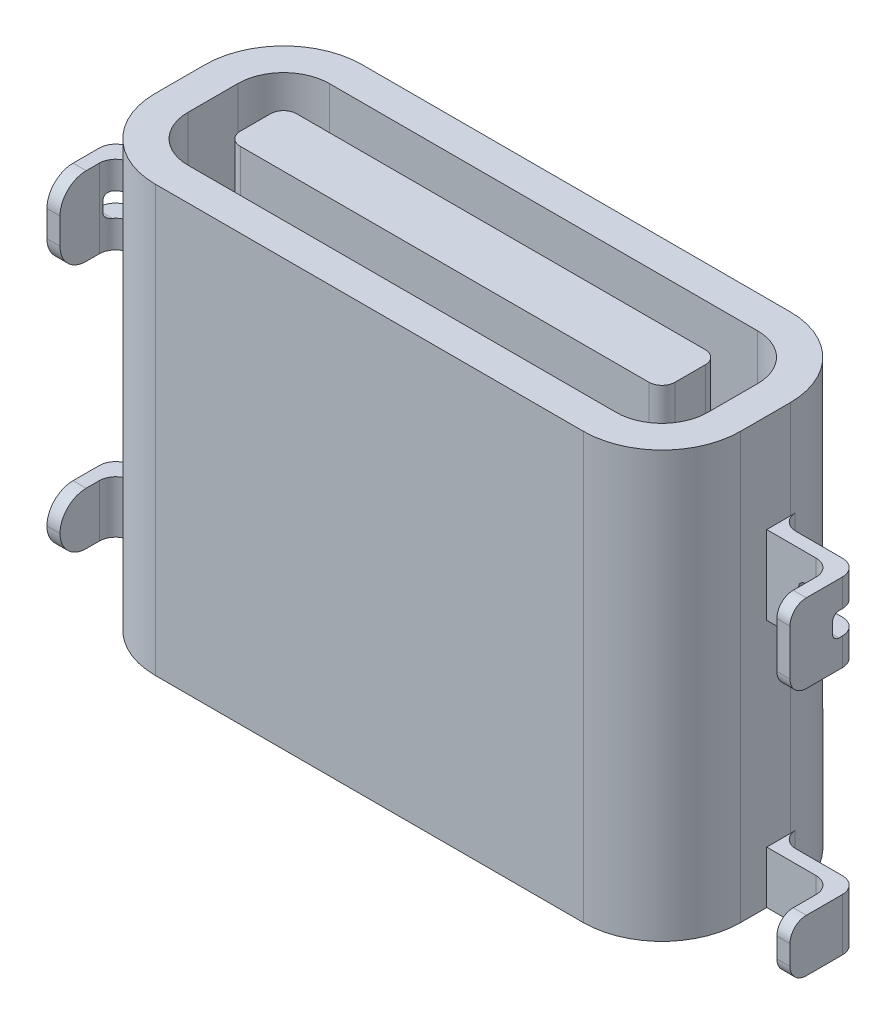
SolidWorks part; units mm, degrees
ref_plane "Front" through (0, 0, 0) normal (0, 0, 1) x (1, 0, 0)
ref_plane "Top" through (0, 0, 0) normal (0, 1, 0) x (1, 0, 0)
ref_plane "Right" through (0, 0, 0) normal (1, 0, 0) x (0, 0, -1)
sketch "Sketch1" plane through (0, 0, 0) normal (0, 1, 0) x (1, 0, 0)
  line L1 (-4.47, -1.58) -> (4.47, -1.58)
  line L2 (-4.47, -1.58) -> (-4.47, 1.58)
  line L3 (-4.47, 1.58) -> (4.47, 1.58)
  line L4 (4.47, -1.58) -> (4.47, 1.58)
  line L5 (-4.47, -1.58) -> (4.47, 1.58) construction
  line L6 (-4.47, 1.58) -> (4.47, -1.58) construction
  point P0 (0, 0)
  dimension "D1" = 8.94
  dimension "D2" = 3.16
extrude "Boss-Extrude1" add sketch "Sketch1" along normal blind 6.5
fillet "Fillet1" radius 1.2 4 edges at (-4.47, 3.25, -1.58) (4.47, 3.25, -1.58) (4.47, 3.25, 1.58) (-4.47, 3.25, 1.58)
shell "Shell1" thickness 0.5 removed face at (0, 6.5, 0)
sketch "Sketch2" plane through (0, 0.5, 0) normal (0, 1, 0) x (1, 0, 0)
  line L0 (0, 0.4305) -> (0, 1.08) construction
  line L1 (-3.3205, -0.4305) -> (3.3205, -0.4305)
  line L2 (-3.3205, -0.4305) -> (-3.3205, 0.4305)
  line L3 (-3.3205, 0.4305) -> (3.3205, 0.4305)
  line L4 (3.3205, -0.4305) -> (3.3205, 0.4305)
  line L5 (-3.3205, -0.4305) -> (3.3205, 0.4305) construction
  line L6 (-3.3205, 0.4305) -> (3.3205, -0.4305) construction
  line L7 (3.27, 1.08) -> (-3.27, 1.08) construction
  line L8 (3.3205, 0) -> (3.97, 0) construction
  line L9 (3.97, -0.38) -> (3.97, 0.38) construction
  point P0 (0, 0)
extrude "Boss-Extrude2" add sketch "Sketch2" along normal blind 6
fillet "Fillet2" radius 0.2 4 edges at (-3.3205, 3.5, 0.4305) (3.3205, 3.5, 0.4305) (3.3205, 3.5, -0.4305) (-3.3205, 3.5, -0.4305)
ref_plane "Plane1" through (0, 0, -0.02) normal (0, 0, 1) x (1, 0, 0)
sketch "Sketch3" plane through (0, 0, -0.02) normal (0, 0, 1) x (1, 0, 0)
  line L0 (-4.47, 0.4) -> (-5.575, 0.4) construction
  line L1 (-4.47, 3.8) -> (-5.575, 3.8)
  line L2 (-4.47, 3.8) -> (-4.47, 5)
  line L3 (-4.47, 5) -> (-5.575, 5)
  line L4 (-5.575, 3.8) -> (-5.575, 5)
  line L5 (-4.47, 0) -> (-5.575, 0)
  line L6 (-4.47, 0) -> (-4.47, 0.8)
  line L7 (-4.47, 0.8) -> (-5.575, 0.8)
  line L8 (-5.575, 0) -> (-5.575, 0.8)
  line L9 (-4.47, 4.4) -> (-5.575, 4.4) construction
  line L10 (-4.47, 0) -> (-4.47, 6.5) construction
  line L11 (-3.27, 6.5) -> (-4.47, 6.5) construction
  line L12 (0, 0) -> (0, 6.5) construction
  line L13 (-3.27, 6.5) -> (3.27, 6.5) construction
  dimension "D1" = 0.8
  dimension "D2" = 1.2
  dimension "D3" = 2.1
  dimension "D4" = 4
extrude "Boss-Extrude3" add sketch "Sketch3" against normal blind 0.2
sketch "Sketch4" plane through (0, 0, -0.02) normal (0, 0, 1) x (1, 0, 0)
  line L0 (-5.575, 3.8) -> (-4.47, 3.8) construction
  line L1 (-5.475, 5) -> (-5.675, 5)
  line L2 (-5.475, 5) -> (-5.475, 3.8)
  line L3 (-5.475, 3.8) -> (-5.675, 3.8)
  line L4 (-5.675, 5) -> (-5.675, 3.8)
  line L5 (-5.575, 0) -> (-4.47, 0) construction
  line L6 (-5.475, 0.8) -> (-5.675, 0.8)
  line L7 (-5.475, 0.8) -> (-5.475, 0)
  line L8 (-5.475, 0) -> (-5.675, 0)
  line L9 (-5.675, 0.8) -> (-5.675, 0)
  line L10 (0, 0) -> (0, 6.5) construction
  line L11 (3.27, 6.5) -> (-3.27, 6.5) construction
  line L12 (-5.575, 3.8) -> (-5.575, 5) construction
  line L13 (-5.575, 0) -> (-5.575, 0.8) construction
  line L14 (-4.47, 5) -> (-5.575, 5) construction
  line L15 (-4.47, 0.8) -> (-5.575, 0.8) construction
  point P23 (0, 0)
  point P24 (6.4041, 4.9545)
  point P27 (0, 0)
  dimension "D2" = 0.2
  dimension "D1" = 5.575
extrude "Boss-Extrude4" add sketch "Sketch4" along normal blind 0.85 and the other way up to surface (0.2 mm away) other way up to face at (-5.0225, 4.4, -0.22)
fillet "Fillet3" radius 0.25 4 edges at (-5.675, 0.4, -0.22) (-5.675, 4.4, -0.22) (-5.475, 0.4, -0.02) (-5.475, 4.4, -0.02)
sketch "Sketch5" plane through (0, 0, -0.22) normal (0, 0, -1) x (-1, 0, 0)
  line L0 (5.425, 3.8) -> (5.425, 5) construction
  line L1 (4.9574, 4.2198) -> (5.8926, 4.2198)
  line L2 (4.9574, 4.2198) -> (4.9574, 4.5802)
  line L3 (4.9574, 4.5802) -> (5.8926, 4.5802)
  line L4 (5.8926, 4.2198) -> (5.8926, 4.5802)
  line L5 (4.9574, 4.2198) -> (5.8926, 4.5802) construction
  line L6 (4.9574, 4.5802) -> (5.8926, 4.2198) construction
  point P0 (5.425, 4.4)
extrude "Cut-Extrude1" cut sketch "Sketch5" against normal blind 0.4
fillet "Fillet4" radius 0.1 4 edges at (-4.9574, 4.2198, -0.12) (-4.9574, 4.5802, -0.12) (-5.5725, 4.2198, 0.18) (-5.5725, 4.5802, 0.18)
fillet "Fillet5" radius 0.4 2 edges at (-4.47, 4.4, -0.22) (-4.47, 0.4, -0.22)
fillet "Fillet6" radius 0.4 4 edges at (-5.575, 0, 0.83) (-5.575, 0.8, 0.83) (-5.575, 5, 0.83) (-5.575, 3.8, 0.83)
sketch "Sketch6" plane through (0, 0, -0.02) normal (0, 0, 1) x (1, 0, 0)
  line L0 (0, 0) -> (-3.6235, 0) construction
  line L1 (0, 0) -> (0, -1.7053) construction
  line L2 (-0.375, -0.7) -> (-0.125, -0.7)
  line L3 (-0.375, -0.7) -> (-0.375, 0)
  line L4 (-0.375, 0) -> (-0.125, 0)
  line L5 (-0.125, -0.7) -> (-0.125, 0)
  line L6 (-0.375, -0.7) -> (-0.125, 0) construction
  line L7 (-0.375, 0) -> (-0.125, -0.7) construction
  line L8 (-0.625, -0.7) -> (-0.625, 0)
  line L9 (-0.875, -0.7) -> (-0.625, -0.7)
  line L10 (-0.875, -0.7) -> (-0.875, 0)
  line L11 (-0.875, 0) -> (-0.625, 0)
  line L12 (-1.125, -0.7) -> (-1.125, 0)
  line L13 (-1.375, -0.7) -> (-1.125, -0.7)
  line L14 (-1.375, -0.7) -> (-1.375, 0)
  line L15 (-1.375, 0) -> (-1.125, 0)
  line L16 (-1.625, -0.7) -> (-1.625, 0)
  line L17 (-1.875, -0.7) -> (-1.625, -0.7)
  line L18 (-1.875, -0.7) -> (-1.875, 0)
  line L19 (-1.875, 0) -> (-1.625, 0)
  line L20 (-2.27, 0) -> (-2.27, -0.7) construction
  line L21 (-2.395, 0) -> (-2.145, 0)
  line L22 (-2.395, 0) -> (-2.395, -0.7)
  line L23 (-2.395, -0.7) -> (-2.145, -0.7)
  line L24 (-2.145, 0) -> (-2.145, -0.7)
  line L25 (-3.32, 0) -> (-3.32, -0.7) construction
  line L26 (-2.6541, 0) -> (-2.4041, 0)
  line L27 (-2.6541, 0) -> (-2.6541, -0.7)
  line L28 (-2.6541, -0.7) -> (-2.4041, -0.7)
  line L29 (-2.4041, 0) -> (-2.4041, -0.7)
  line L30 (-2.9367, 0) -> (-3.1867, 0)
  line L31 (-2.9367, 0) -> (-2.9367, -0.7)
  line L32 (-2.9367, -0.7) -> (-3.1867, -0.7)
  line L33 (-3.1867, 0) -> (-3.1867, -0.7)
  line L34 (-3.445, 0) -> (-3.195, 0)
  line L35 (-3.445, 0) -> (-3.445, -0.7)
  line L36 (-3.445, -0.7) -> (-3.195, -0.7)
  line L37 (-3.195, 0) -> (-3.195, -0.7)
  point P3 (-0.25, -0.35)
  dimension "D1" = 0.25
  dimension "D2" = 0.25
  dimension "D3" = 0.7
  dimension "D5" = 2.27
  dimension "D6" = 1.05
  dimension "D4" = 4
extrude "Boss-Extrude5" add sketch "Sketch6" against normal blind 0.15
ref_plane "Plane2" through (0, 0, 0) normal (-1, 0, 0) x (0, 0, 1)
mirror "Mirror3" about plane through (0, 0, 0) normal (-1, 0, 0) of "Boss-Extrude5"
mirror "Mirror6" about plane through (0, 0, 0) normal (-1, 0, 0) of "Boss-Extrude4", "Boss-Extrude3"
mirror "Mirror8" about plane through (0, 0, 0) normal (-1, 0, 0) of "Cut-Extrude1"
fillet "Fillet7" radius 0.25 11 edges at (5.575, 5, 0.83) (5.575, 3.8, 0.83) (5.575, 0.8, 0.83) (5.575, 0, 0.83) (4.47, 4.4, -0.22) (4.47, 0.4, -0.22) (5.475, 0.4, -0.02) (5.475, 4.0099, -0.02) (5.675, 0.4, -0.22) (5.675, 4.7901, -0.22) (5.675, 4.0099, -0.22)
fillet "Fillet8" radius 0.1 4 edges at (5.5725, 4.5802, 0.18) (5.5725, 4.2198, 0.18) (4.9574, 4.2198, -0.12) (4.9574, 4.5802, -0.12)
ref_plane "Plane3" through (0, -0.35, 0) normal (0, -1, 0) x (-1, 0, 0)
ref_axis "Axis1" through (0, -0.35, -0.418) along (0, 0, 1)
ref_point "Point1"
equation "\"D1@Sketch4\"=11.15/2"
